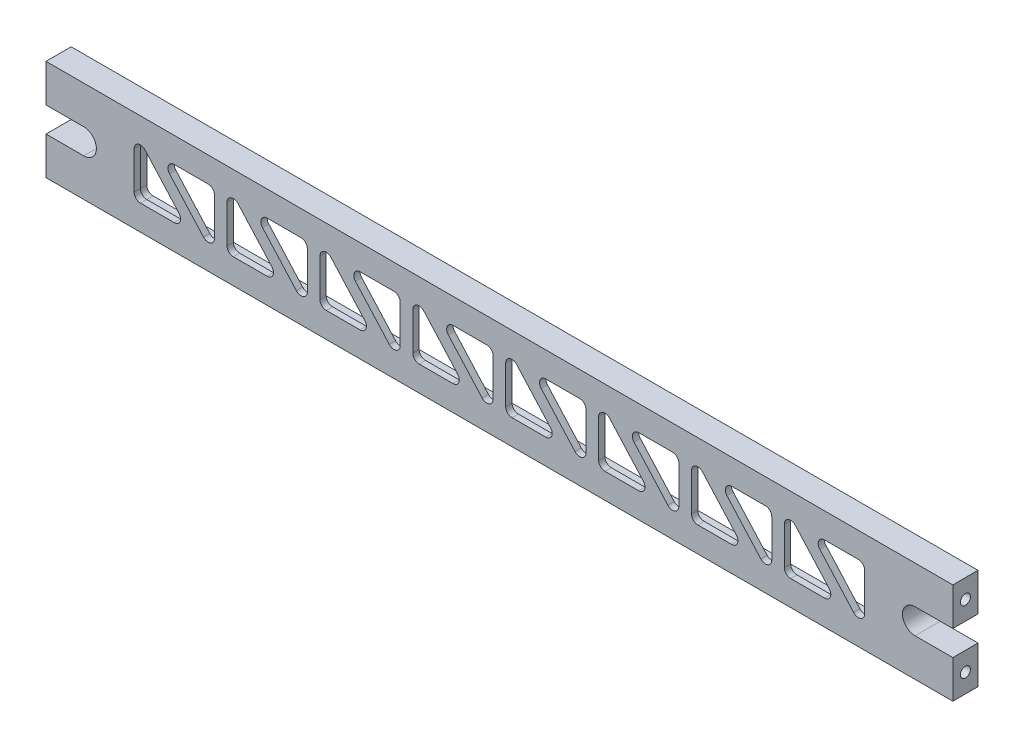
SolidWorks part; units mm, degrees
material "6061 Alloy"
ref_plane "Front Plane" through (0, 0, 0) normal (0, 0, 1) x (1, 0, 0)
ref_plane "Top Plane" through (0, 0, 0) normal (0, 1, 0) x (1, 0, 0)
ref_plane "Right Plane" through (0, 0, 0) normal (1, 0, 0) x (0, 0, -1)
sketch "Sketch1" plane through (0, 0, 0) normal (1, 0, 0) x (0, 0, -1)
  line L1 (0, 0) -> (12.7, 0)
  line L2 (0, 0) -> (0, 50.8)
  line L3 (0, 50.8) -> (12.7, 50.8)
  line L4 (12.7, 0) -> (12.7, 50.8)
  dimension "D1" = 12.7
  dimension "D2" = 50.8
extrude "Boss-Extrude1" add sketch "Sketch1" along normal mid plane 457.2
hole_wizard "1/4-20 Tapped Hole1" positions "3DSketch1" profile "Sketch2" tap size "1/4-20" standard "ANSI Inch"
sketch3d "3DSketch1"
  line L2 (228.6, 9.525, -6.35) -> (228.6, 41.275, -6.35) construction
  line L4 (228.6, 41.275, -6.35) -> (228.6, 50.8, -6.35) construction
  line L5 (228.6, 50.8, -12.7) -> (228.6, 50.8, 0) construction
  line L8 (228.6, 9.525, -6.35) -> (228.6, 0, -6.35) construction
  line L9 (228.6, 0, 0) -> (228.6, 0, -12.7) construction
  point P0 (228.6, 41.275, -6.35)
  point P2 (228.6, 9.525, -6.35)
  point P4 (-228.6, 9.525, -6.35)
  point P6 (-228.6, 41.275, -6.35)
  dimension "D1" = 31.75
sketch "Sketch2" plane through (228.6, 41.275, -6.35) normal (0, 1, 0) x (0, 0, -1)
  line L0 (0, 0) -> (0, 30.7438)
  line L1 (0, 30.7438) -> (2.5527, 29.21)
  line L2 (2.5527, 29.21) -> (2.5527, 0)
  line L5 (2.5527, 0) -> (0, 0)
  line L10 (0, 30.7438) -> (-2.5527, 29.21) construction
  line L11 (0, -6.35) -> (0, 107.95) construction
  dimension "Tap Drill Dia." = 5.1054
  dimension "Tap Drill Depth" = 29.21
  dimension "Drill Angle" = 118
sketch "Sketch4" plane through (0, 0, -12.7) normal (0, 0, -1) x (-1, 0, 0)
  line L0 (0, 0) -> (0, 6.35) construction
  line L1 (187.325, 44.45) -> (-187.325, 44.45)
  line L2 (190.5, 41.275) -> (190.5, 9.525)
  line L3 (187.325, 6.35) -> (-187.325, 6.35)
  line L4 (-190.5, 41.275) -> (-190.5, 9.525)
  line L5 (-228.6, 0) -> (228.6, 0) construction
  line L6 (0, 44.45) -> (0, 50.8) construction
  line L7 (-228.6, 50.8) -> (228.6, 50.8) construction
  line L8 (228.6, 25.4) -> (190.5, 25.4) construction
  line L9 (228.6, 0) -> (228.6, 50.8) construction
  line L10 (-228.6, 25.4) -> (-190.5, 25.4) construction
  line L11 (-228.6, 0) -> (-228.6, 50.8) construction
  arc A0 (-187.325, 6.35) -> (-190.5, 9.525) centre (-187.325, 9.525) cw
  arc A1 (-187.325, 44.45) -> (-190.5, 41.275) centre (-187.325, 41.275) ccw
  arc A2 (190.5, 9.525) -> (187.325, 6.35) centre (187.325, 9.525) cw
  arc A3 (187.325, 44.45) -> (190.5, 41.275) centre (187.325, 41.275) cw
  dimension "D1" = 3.175
  dimension "D2" = 6.35
  dimension "D3" = 38.1
extrude "Cut-Extrude1" cut sketch "Sketch4" against normal blind 9.525
sketch "Sketch5" plane through (0, 0, -3.175) normal (0, 0, -1) x (-1, 0, 0)
  line L0 (-184.15, 34.925) -> (-184.15, 15.875)
  line L1 (-178.6108, 13.7558) -> (-161.5349, 32.8058)
  line L2 (-163.8991, 38.1) -> (-180.975, 38.1)
  line L3 (-166.2839, 17.9942) -> (-149.208, 37.0442)
  line L4 (-143.6688, 34.925) -> (-143.6688, 15.875)
  line L5 (-146.8438, 12.7) -> (-163.9197, 12.7)
  line L6 (187.325, 44.45) -> (-187.325, 44.45) construction
  line L7 (-187.325, 6.35) -> (187.325, 6.35) construction
  line L8 (-190.5, 25.4) -> (-184.15, 25.4) construction
  line L9 (-190.5, 41.275) -> (-190.5, 9.525) construction
  line L10 (-170.0728, 23.2808) -> (-165.3444, 19.0423) construction
  line L11 (-143.6688, 25.4) -> (-137.3188, 25.4) construction
  line L12 (-137.3188, 34.925) -> (-137.3188, 15.875)
  line L13 (-117.0678, 38.1) -> (-134.1438, 38.1)
  line L14 (-131.7795, 13.7558) -> (-114.7036, 32.8058)
  line L15 (-123.2416, 23.2808) -> (-118.5131, 19.0423) construction
  line L16 (-119.4526, 17.9942) -> (-102.3767, 37.0442)
  line L17 (-96.8375, 34.925) -> (-96.8375, 15.875)
  line L18 (-100.0125, 12.7) -> (-117.0884, 12.7)
  line L19 (-96.8375, 25.4) -> (-90.4875, 25.4) construction
  line L20 (-90.4875, 34.925) -> (-90.4875, 15.875)
  line L21 (-70.2366, 38.1) -> (-87.3125, 38.1)
  line L22 (-84.9483, 13.7558) -> (-67.8724, 32.8058)
  line L23 (-76.4103, 23.2808) -> (-71.6819, 19.0423) construction
  line L24 (-72.6214, 17.9942) -> (-55.5455, 37.0442)
  line L25 (-50.0063, 34.925) -> (-50.0063, 15.875)
  line L26 (-53.1812, 12.7) -> (-70.2572, 12.7)
  line L27 (-50.0063, 25.4) -> (-43.6563, 25.4) construction
  line L28 (-43.6563, 34.925) -> (-43.6563, 15.875)
  line L29 (-23.4053, 38.1) -> (-40.4813, 38.1)
  line L30 (-38.117, 13.7558) -> (-21.0411, 32.8058)
  line L31 (-29.5791, 23.2808) -> (-24.8506, 19.0423) construction
  line L32 (-25.7901, 17.9942) -> (-8.7142, 37.0442)
  line L33 (-3.175, 34.925) -> (-3.175, 15.875)
  line L34 (-6.35, 12.7) -> (-23.4259, 12.7)
  line L35 (-3.175, 25.4) -> (3.175, 25.4) construction
  line L36 (3.175, 34.925) -> (3.175, 15.875)
  line L37 (23.4259, 38.1) -> (6.35, 38.1)
  line L38 (8.7142, 13.7558) -> (25.7901, 32.8058)
  line L39 (17.2522, 23.2808) -> (21.9806, 19.0423) construction
  line L40 (21.0411, 17.9942) -> (38.117, 37.0442)
  line L41 (43.6562, 34.925) -> (43.6562, 15.875)
  line L42 (40.4812, 12.7) -> (23.4053, 12.7)
  line L43 (43.6562, 25.4) -> (50.0062, 25.4) construction
  line L44 (50.0062, 34.925) -> (50.0062, 15.875)
  line L45 (70.2572, 38.1) -> (53.1812, 38.1)
  line L46 (55.5455, 13.7558) -> (72.6214, 32.8058)
  line L47 (64.0834, 23.2808) -> (68.8119, 19.0423) construction
  line L48 (67.8724, 17.9942) -> (84.9483, 37.0442)
  line L49 (90.4875, 34.925) -> (90.4875, 15.875)
  line L50 (87.3125, 12.7) -> (70.2366, 12.7)
  line L51 (90.4875, 25.4) -> (96.8375, 25.4) construction
  line L52 (96.8375, 34.925) -> (96.8375, 15.875)
  line L53 (117.0884, 38.1) -> (100.0125, 38.1)
  line L54 (102.3767, 13.7558) -> (119.4526, 32.8058)
  line L55 (110.9147, 23.2808) -> (115.6431, 19.0423) construction
  line L56 (114.7036, 17.9942) -> (131.7795, 37.0442)
  line L57 (137.3187, 34.925) -> (137.3187, 15.875)
  line L58 (134.1438, 12.7) -> (117.0678, 12.7)
  line L59 (137.3187, 25.4) -> (143.6687, 25.4) construction
  line L60 (143.6687, 34.925) -> (143.6687, 15.875)
  line L61 (163.9197, 38.1) -> (146.8437, 38.1)
  line L62 (149.208, 13.7558) -> (166.2839, 32.8058)
  line L63 (157.7459, 23.2808) -> (162.4744, 19.0423) construction
  line L64 (161.5349, 17.9942) -> (178.6108, 37.0442)
  line L65 (184.15, 34.925) -> (184.15, 15.875)
  line L66 (180.975, 12.7) -> (163.8991, 12.7)
  line L67 (190.5, 25.4) -> (184.15, 25.4) construction
  line L69 (190.5, 9.525) -> (190.5, 41.275) construction
  arc A0 (-166.2839, 17.9942) -> (-163.9197, 12.7) centre (-163.9197, 15.875) ccw
  arc A1 (-143.6688, 15.875) -> (-146.8438, 12.7) centre (-146.8438, 15.875) cw
  arc A2 (-149.208, 37.0442) -> (-143.6688, 34.925) centre (-146.8438, 34.925) cw
  arc A3 (-161.5349, 32.8058) -> (-163.8991, 38.1) centre (-163.8991, 34.925) ccw
  arc A4 (-184.15, 15.875) -> (-178.6108, 13.7558) centre (-180.975, 15.875) ccw
  arc A5 (-184.15, 34.925) -> (-180.975, 38.1) centre (-180.975, 34.925) cw
  arc A6 (-137.3188, 34.925) -> (-134.1438, 38.1) centre (-134.1438, 34.925) cw
  arc A7 (-114.7036, 32.8058) -> (-117.0678, 38.1) centre (-117.0678, 34.925) ccw
  arc A8 (-137.3188, 15.875) -> (-131.7795, 13.7558) centre (-134.1438, 15.875) ccw
  arc A9 (-102.3767, 37.0442) -> (-96.8375, 34.925) centre (-100.0125, 34.925) cw
  arc A10 (-96.8375, 15.875) -> (-100.0125, 12.7) centre (-100.0125, 15.875) cw
  arc A11 (-119.4526, 17.9942) -> (-117.0884, 12.7) centre (-117.0884, 15.875) ccw
  arc A12 (-90.4875, 34.925) -> (-87.3125, 38.1) centre (-87.3125, 34.925) cw
  arc A13 (-67.8724, 32.8058) -> (-70.2366, 38.1) centre (-70.2366, 34.925) ccw
  arc A14 (-90.4875, 15.875) -> (-84.9483, 13.7558) centre (-87.3125, 15.875) ccw
  arc A15 (-55.5455, 37.0442) -> (-50.0063, 34.925) centre (-53.1812, 34.925) cw
  arc A16 (-50.0063, 15.875) -> (-53.1812, 12.7) centre (-53.1812, 15.875) cw
  arc A17 (-72.6214, 17.9942) -> (-70.2572, 12.7) centre (-70.2572, 15.875) ccw
  arc A18 (-43.6563, 34.925) -> (-40.4813, 38.1) centre (-40.4813, 34.925) cw
  arc A19 (-21.0411, 32.8058) -> (-23.4053, 38.1) centre (-23.4053, 34.925) ccw
  arc A20 (-43.6563, 15.875) -> (-38.117, 13.7558) centre (-40.4813, 15.875) ccw
  arc A21 (-8.7142, 37.0442) -> (-3.175, 34.925) centre (-6.35, 34.925) cw
  arc A22 (-3.175, 15.875) -> (-6.35, 12.7) centre (-6.35, 15.875) cw
  arc A23 (-25.7901, 17.9942) -> (-23.4259, 12.7) centre (-23.4259, 15.875) ccw
  arc A24 (3.175, 34.925) -> (6.35, 38.1) centre (6.35, 34.925) cw
  arc A25 (25.7901, 32.8058) -> (23.4259, 38.1) centre (23.4259, 34.925) ccw
  arc A26 (3.175, 15.875) -> (8.7142, 13.7558) centre (6.35, 15.875) ccw
  arc A27 (38.117, 37.0442) -> (43.6562, 34.925) centre (40.4812, 34.925) cw
  arc A28 (43.6562, 15.875) -> (40.4812, 12.7) centre (40.4812, 15.875) cw
  arc A29 (21.0411, 17.9942) -> (23.4053, 12.7) centre (23.4053, 15.875) ccw
  arc A30 (50.0062, 34.925) -> (53.1812, 38.1) centre (53.1812, 34.925) cw
  arc A31 (72.6214, 32.8058) -> (70.2572, 38.1) centre (70.2572, 34.925) ccw
  arc A32 (50.0062, 15.875) -> (55.5455, 13.7558) centre (53.1812, 15.875) ccw
  arc A33 (84.9483, 37.0442) -> (90.4875, 34.925) centre (87.3125, 34.925) cw
  arc A34 (90.4875, 15.875) -> (87.3125, 12.7) centre (87.3125, 15.875) cw
  arc A35 (67.8724, 17.9942) -> (70.2366, 12.7) centre (70.2366, 15.875) ccw
  arc A36 (96.8375, 34.925) -> (100.0125, 38.1) centre (100.0125, 34.925) cw
  arc A37 (119.4526, 32.8058) -> (117.0884, 38.1) centre (117.0884, 34.925) ccw
  arc A38 (96.8375, 15.875) -> (102.3767, 13.7558) centre (100.0125, 15.875) ccw
  arc A39 (131.7795, 37.0442) -> (137.3187, 34.925) centre (134.1438, 34.925) cw
  arc A40 (137.3187, 15.875) -> (134.1438, 12.7) centre (134.1438, 15.875) cw
  arc A41 (114.7036, 17.9942) -> (117.0678, 12.7) centre (117.0678, 15.875) ccw
  arc A42 (143.6687, 34.925) -> (146.8437, 38.1) centre (146.8437, 34.925) cw
  arc A43 (166.2839, 32.8058) -> (163.9197, 38.1) centre (163.9197, 34.925) ccw
  arc A44 (143.6687, 15.875) -> (149.208, 13.7558) centre (146.8437, 15.875) ccw
  arc A45 (178.6108, 37.0442) -> (184.15, 34.925) centre (180.975, 34.925) cw
  arc A46 (184.15, 15.875) -> (180.975, 12.7) centre (180.975, 15.875) cw
  arc A47 (161.5349, 17.9942) -> (163.8991, 12.7) centre (163.8991, 15.875) ccw
  point P18 (-146.8438, 38.1)
  point P19 (-180.975, 12.7)
  dimension "D1" = 3.175
  dimension "D2" = 6.35
  dimension "D3" = 6.35
  dimension "D4" = 6.35
  dimension "D5" = 8
extrude "Cut-Extrude2" cut sketch "Sketch5" against normal through all
sketch "Sketch6" plane through (0, 0, 0) normal (0, 0, 1) x (1, 0, 0)
  line L0 (0, 0) -> (0, 50.8) construction
  line L1 (228.6, 50.8) -> (-228.6, 50.8) construction
  line L2 (-209.55, 31.75) -> (-228.6, 31.75)
  line L3 (-228.6, 50.8) -> (-228.6, 0) construction
  line L4 (-228.6, 31.75) -> (-228.6, 19.05)
  line L5 (-228.6, 19.05) -> (-209.55, 19.05)
  line L6 (228.6, 19.05) -> (209.55, 19.05)
  line L8 (228.6, 31.75) -> (228.6, 19.05)
  line L9 (209.55, 31.75) -> (228.6, 31.75)
  arc A0 (-209.55, 19.05) -> (-209.55, 31.75) centre (-209.55, 25.4) ccw
  arc A1 (209.55, 19.05) -> (209.55, 31.75) centre (209.55, 25.4) cw
  point P8 (-228.6, 25.4)
  point P18 (228.6, 25.4)
  dimension "D1" = 12.7
  dimension "D2" = 19.05
extrude "Cut-Extrude3" cut sketch "Sketch6" against normal through all
